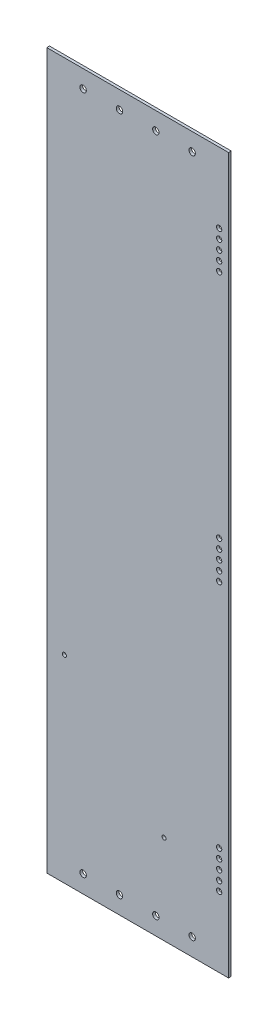
SolidWorks part; units mm, degrees
material "5052-H32"
ref_plane "Front Plane" through (0, 0, 0) normal (0, 0, 1) x (1, 0, 0)
ref_plane "Top Plane" through (0, 0, 0) normal (0, 1, 0) x (1, 0, 0)
ref_plane "Right Plane" through (0, 0, 0) normal (1, 0, 0) x (0, 0, -1)
sketch "Sketch1" plane through (0, 0, 0) normal (0, 0, 1) x (1, 0, 0)
  line L0 (55, 0) -> (-55, 0) construction
  line L1 (-77.5, 304.8) -> (77.5, 304.8)
  line L2 (-77.5, 304.8) -> (-77.5, -304.8)
  line L3 (-77.5, -304.8) -> (77.5, -304.8)
  line L4 (77.5, 304.8) -> (77.5, -304.8)
  line L5 (-77.5, 304.8) -> (77.5, -304.8) construction
  line L6 (-77.5, -304.8) -> (77.5, 304.8) construction
  point P0 (0, 0)
  point P5 (69.5, 244.8)
  point P7 (69.5, 228.8)
  point P8 (69.5, 236.8)
  point P9 (69.5, 220.8)
  point P10 (69.5, 212.8)
  point P11 (69.5, 8)
  point P12 (69.5, 16)
  point P13 (69.5, -212.8)
  point P14 (69.5, -228.8)
  point P15 (69.5, -220.8)
  point P16 (69.5, -236.8)
  point P17 (69.5, -244.8)
  point P18 (69.5, -8)
  point P19 (69.5, -16)
  point P20 (-46.5, 289.795)
  point P21 (-15.5, 289.795)
  point P22 (69.5, 0)
  point P23 (15.5, 289.795)
  point P24 (46.5, 289.795)
  point P25 (22.5, -228.6)
  point P26 (-62.5, -136.1)
  point P29 (46.5, -289.795)
  point P30 (15.5, -289.795)
  point P31 (-15.5, -289.795)
  point P32 (-46.5, -289.795)
  point P33 (-38.6744, -258.4517)
  point P34 (19.7443, -225.5915)
  point P35 (44.1851, -143.5224)
  point P36 (21.2612, -236.8)
  point P37 (-49.1887, -145.3249)
  dimension "D1" = 609.6
  dimension "D2" = 155
  dimension "D3" = 8
  dimension "D4" = 60
  dimension "D5" = 8
  dimension "D6" = 8
  dimension "D7" = 8
  dimension "D8" = 8
  dimension "D9" = 60
  dimension "D10" = 8
  dimension "D11" = 8
  dimension "D12" = 8
  dimension "D13" = 8
  dimension "D14" = 8
  dimension "D15" = 8
  dimension "D16" = 8
  dimension "D17" = 8
  dimension "D18" = 8
  dimension "D19" = 8
  dimension "D20" = 31
  dimension "D21" = 31
  dimension "D22" = 31
  dimension "D23" = 31
  dimension "D24" = 15.005
  dimension "D25" = 92.5
  dimension "D26" = 85
  dimension "D27" = 76.2
  dimension "D28" = 15
extrude "Boss-Extrude1" add sketch "Sketch1" along normal blind 2.305
hole_wizard "M4 Clearance Hole1" positions "Sketch3" profile "Sketch5" hole size "M4" standard "ANSI Metric" end condition through all
sketch "Sketch3" plane through (0, 0, 2.305) normal (0, 0, 1) x (1, 0, 0)
  point P4 (69.5, 228.8)
  point P9 (69.5, 244.8)
  point P12 (69.5, 236.8)
  point P15 (69.5, 220.8)
  point P18 (69.5, 212.8)
  point P21 (69.5, 16)
  point P24 (69.5, 8)
  point P27 (69.5, 0)
  point P30 (69.5, -8)
  point P33 (69.5, -16)
  point P36 (69.5, -212.8)
  point P39 (69.5, -220.8)
  point P42 (69.5, -228.8)
  point P45 (69.5, -236.8)
  point P48 (69.5, -244.8)
sketch "Sketch5" plane through (69.5, 228.8, 2.305) normal (1, 0, 0) x (0, -1, 0)
  line L0 (0, 0) -> (0, 2.305)
  line L1 (0, 2.305) -> (2.25, 2.305)
  line L2 (2.25, 2.305) -> (2.25, 0)
  line L5 (2.25, 0) -> (0, 0)
  line L11 (0, -6.35) -> (0, 107.95) construction
  dimension "Thru Hole Dia." = 4.5
  dimension "Thru Hole Depth" = 2.305
hole_wizard "M5 Clearance Hole1" positions "Sketch6" profile "Sketch7" hole size "M5" standard "ANSI Metric" end condition through all
sketch "Sketch6" plane through (0, 0, 2.305) normal (0, 0, 1) x (1, 0, 0)
  point P0 (-46.5, -289.795)
  point P3 (-15.5, -289.795)
  point P6 (15.5, -289.795)
  point P9 (46.5, -289.795)
  point P12 (-46.5, 289.795)
  point P15 (-15.5, 289.795)
  point P18 (15.5, 289.795)
  point P21 (46.5, 289.795)
sketch "Sketch7" plane through (-46.5, -289.795, 2.305) normal (1, 0, 0) x (0, -1, 0)
  line L0 (0, 0) -> (0, 2.305)
  line L1 (0, 2.305) -> (2.75, 2.305)
  line L2 (2.75, 2.305) -> (2.75, 0)
  line L5 (2.75, 0) -> (0, 0)
  line L11 (0, -6.35) -> (0, 107.95) construction
  dimension "Thru Hole Dia." = 5.5
  dimension "Thru Hole Depth" = 2.305
hole_wizard "Ø3.5 (3.5) Diameter Hole1" positions "Sketch8" profile "Sketch9" hole size "Ø3.5" standard "ANSI Metric" end condition through all
sketch "Sketch8" plane through (0, 0, 0) normal (0, 0, -1) x (-1, 0, 0)
  point P0 (-22.5, -228.6)
  point P3 (62.5, -136.1)
sketch "Sketch9" plane through (22.5, -228.6, 0) normal (1, 0, 0) x (0, 1, 0)
  line L0 (0, 0) -> (0, 2.305)
  line L1 (0, 2.305) -> (1.75, 2.305)
  line L2 (1.75, 2.305) -> (1.75, 0)
  line L5 (1.75, 0) -> (0, 0)
  line L11 (0, -6.35) -> (0, 107.95) construction
  dimension "Thru Hole Dia." = 3.5
  dimension "Thru Hole Depth" = 2.305
